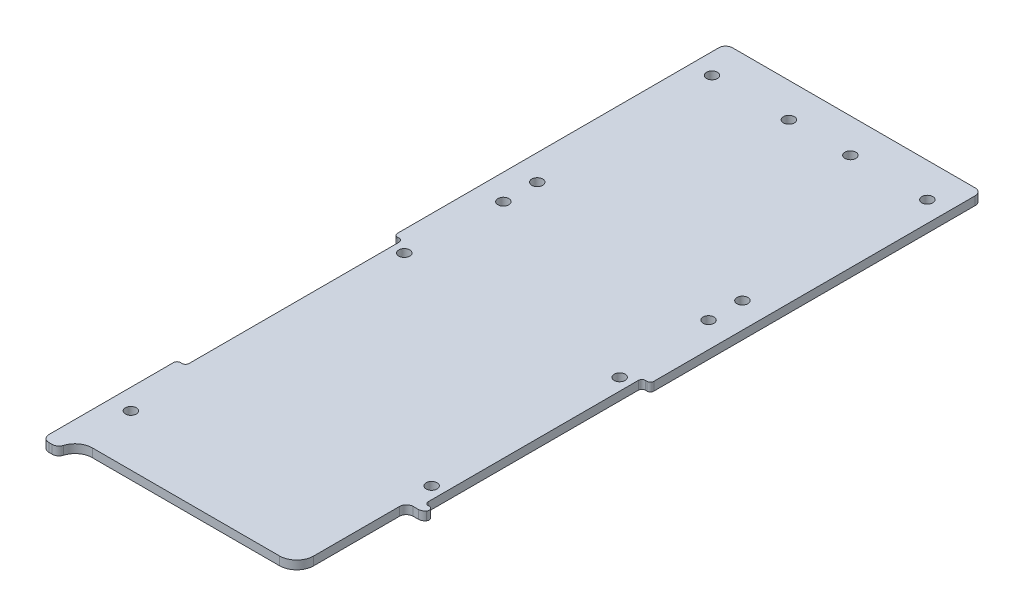
SolidWorks part; units mm, degrees
ref_plane "Front Plane" through (0, 0, 0) normal (0, 0, 1) x (1, 0, 0)
ref_plane "Top Plane" through (0, 0, 0) normal (0, 1, 0) x (1, 0, 0)
ref_plane "Right Plane" through (0, 0, 0) normal (1, 0, 0) x (0, 0, -1)
sketch "Sketch1" plane through (0, 0, 0) normal (0, 1, 0) x (1, 0, 0)
  line L0 (-39.9997, 0) -> (-39.9997, 114.3) construction
  line L1 (-47.625, 127) -> (47.625, 127)
  line L2 (-47.625, 127) -> (-47.625, -127)
  line L3 (-47.625, -127) -> (47.625, -127)
  line L4 (47.625, 127) -> (47.625, -127)
  line L5 (-47.625, 127) -> (47.625, -127) construction
  line L6 (-47.625, -127) -> (47.625, 127) construction
  line L7 (0, 0) -> (0, 127) construction
  line L8 (-39.9997, 0) -> (-39.9997, -101.6) construction
  line L9 (-39.9997, 0) -> (0, 0) construction
  line L10 (-41.275, -127) -> (-41.275, -120.65)
  line L11 (-41.275, -120.65) -> (41.275, -120.65)
  line L12 (41.275, -120.65) -> (41.275, -127)
  line L13 (-39.9997, 114.3) -> (-11.4247, 114.3) construction
  line L14 (39.9997, 114.3) -> (11.4247, 114.3) construction
  circle A0 centre (-39.9997, 114.3) radius 2.032
  circle A1 centre (-39.9997, 0) radius 2.032
  circle A2 centre (-39.9997, -101.6) radius 2.032
  circle A3 centre (39.9997, -101.6) radius 2.032
  circle A4 centre (39.9997, 0) radius 2.032
  circle A5 centre (39.9997, 114.3) radius 2.032
  circle A6 centre (-11.4247, 114.3) radius 2.032
  circle A7 centre (11.4247, 114.3) radius 2.032
  circle A8 centre (-39.9997, -69.85) radius 2.032
  circle A9 centre (39.9997, -69.85) radius 2.032
  point P0 (0, 0)
  dimension "D4" = 4.064
  dimension "D10" = 28.575
  dimension "D1" = 95.25
  dimension "D2" = 254
  dimension "D3" = 7.6253
  dimension "D5" = 12.7
  dimension "D6" = 25.4
  dimension "D7" = 6.35
  dimension "D8" = 6.35
  dimension "D9" = 6.35
  dimension "D11" = 69.85
extrude "Boss-Extrude1" add sketch "Sketch1" along normal blind 3.175 contours L4 L1 L2 L3 A4 A0 A1 A2 A3 A5 | A8 | A3 region at (0, 0, -2.6944) region at (39.9997, 0, 101.6) region at (-39.9997, 0, 69.85)
fillet "Fillet1" radius 2.54 4 edges at (-47.625, 1.5875, -127) (47.625, 1.5875, -127) (47.625, 1.5875, 127) (-47.625, 1.5875, 127)
fillet "Fillet2" radius 2.54 2 edges at (41.275, 1.5875, 127) (-41.275, 1.5875, 127)
fillet "Fillet3" radius 6.35 2 edges at (41.275, 1.5875, 120.65) (-41.275, 1.5875, 120.65)
sketch "Sketch2" plane through (0, 0, 0) normal (0, -1, 0) x (1, 0, 0)
  line L1 (43.815, 127) -> (45.085, 127) construction
  line L2 (40.6451, 123.5787) -> (40.6451, 79.8881)
  line L3 (40.6451, 79.8881) -> (47.625, 79.8881)
  line L11 (47.625, -124.46) -> (47.625, 124.46) construction
  line L12 (43.815, 127) -> (45.085, 127)
  line L13 (47.625, 79.8881) -> (47.625, 124.46)
  arc A0 (35.2956, 120.65) -> (41.3809, 125.1857) centre (35.2956, 127) ccw construction
  arc A1 (43.815, 127) -> (41.3809, 125.1857) centre (43.815, 124.46) ccw construction
  arc A2 (47.625, 124.46) -> (45.085, 127) centre (45.085, 124.46) ccw construction
  arc A3 (40.6451, 123.5787) -> (41.3809, 125.1857) centre (35.2956, 127) ccw
  arc A4 (43.815, 127) -> (41.3809, 125.1857) centre (43.815, 124.46) ccw
  arc A5 (47.625, 124.46) -> (45.085, 127) centre (45.085, 124.46) ccw
  dimension "D2" = 47.1119
  dimension "D1" = 6.9799
extrude "Cut-Extrude1" cut sketch "Sketch2" against normal through all
fillet "Fillet4" radius 6.35 1 edges at (40.6451, 1.5875, 123.5787)
fillet "Fillet5" radius 2.54 2 edges at (47.625, 1.5875, 79.8881) (40.6451, 1.5875, 79.8881)
sketch "Sketch3" plane through (0, 0, 0) normal (0, -1, 0) x (1, 0, 0)
  line L0 (-36.305, -49.7791) -> (-39.9118, -49.7791) construction
  line L1 (-40.4198, -49.276) -> (-40.4198, -45.7043) construction
  line L2 (-35.797, -45.7043) -> (-35.797, -49.276) construction
  line L3 (-39.9118, -45.2013) -> (-36.305, -45.2013) construction
  line L4 (-36.305, -37.2027) -> (-39.9118, -37.2027) construction
  line L5 (-35.797, -33.1279) -> (-35.797, -36.6996) construction
  line L6 (-40.4198, -36.6996) -> (-40.4198, -33.1279) construction
  line L7 (-39.9118, -32.6249) -> (-36.305, -32.6249) construction
  line L8 (36.2882, -32.6249) -> (39.895, -32.6249) construction
  line L9 (40.403, -33.1279) -> (40.403, -36.6996) construction
  line L10 (39.895, -37.2027) -> (36.2882, -37.2027) construction
  line L11 (35.7802, -36.6996) -> (35.7802, -33.1279) construction
  line L12 (36.2882, -45.2013) -> (39.895, -45.2013) construction
  line L13 (35.7802, -49.276) -> (35.7802, -45.7043) construction
  line L14 (40.403, -45.7043) -> (40.403, -49.276) construction
  line L15 (39.895, -49.7791) -> (36.2882, -49.7791) construction
  line L16 (-36.305, -49.7791) -> (-39.9118, -49.7791)
  line L17 (-40.4198, -49.276) -> (-40.4198, -45.7043)
  line L18 (-35.797, -45.7043) -> (-35.797, -49.276)
  line L19 (-39.9118, -45.2013) -> (-36.305, -45.2013)
  line L20 (-36.305, -37.2027) -> (-39.9118, -37.2027)
  line L21 (-35.797, -33.1279) -> (-35.797, -36.6996)
  line L22 (-40.4198, -36.6996) -> (-40.4198, -33.1279)
  line L23 (-39.9118, -32.6249) -> (-36.305, -32.6249)
  line L24 (36.2882, -32.6249) -> (39.895, -32.6249)
  line L25 (40.403, -33.1279) -> (40.403, -36.6996)
  line L26 (39.895, -37.2027) -> (36.2882, -37.2027)
  line L27 (35.7802, -36.6996) -> (35.7802, -33.1279)
  line L28 (36.2882, -45.2013) -> (39.895, -45.2013)
  line L29 (35.7802, -49.276) -> (35.7802, -45.7043)
  line L30 (40.403, -45.7043) -> (40.403, -49.276)
  line L31 (39.895, -49.7791) -> (36.2882, -49.7791)
  line L32 (-47.625, -25.836) -> (47.625, -25.836)
  line L33 (-47.625, -124.46) -> (-47.625, 124.46) construction
  line L34 (47.625, -124.46) -> (47.625, 77.3481) construction
  line L35 (0, -25.836) -> (0, -56.0686) construction
  line L1362 (-40.4198, -34.9138) -> (-35.797, -34.9138)
  line L1857 (-38.1084, -32.6249) -> (-38.1084, -37.2027)
  line L1858 (-38.1084, -45.2013) -> (-38.1084, -49.7791)
  line L1859 (-40.4198, -47.4902) -> (-35.797, -47.4902)
  circle A0 centre (-38.1084, -34.9138) radius 2.032
  circle A1 centre (-38.1084, -47.4902) radius 2.032
  circle A2 centre (38.1084, -47.4902) radius 2.032
  circle A3 centre (38.1084, -34.9138) radius 2.032
  ellipse E0 centre (-39.9118, -45.7043) end of major axis (-39.4038, -45.7043) minor radius 0.5031 (-39.9118, -45.2013) -> (-40.4198, -45.7043) ccw construction
  ellipse E1 centre (-39.9118, -49.276) end of major axis (-39.4038, -49.276) minor radius 0.5031 (-40.4198, -49.276) -> (-39.9118, -49.7791) ccw construction
  ellipse E6 centre (-36.305, -49.276) end of major axis (-35.797, -49.276) minor radius 0.5031 (-36.305, -49.7791) -> (-35.797, -49.276) ccw construction
  ellipse E7 centre (-36.305, -45.7043) end of major axis (-35.797, -45.7043) minor radius 0.5031 (-35.797, -45.7043) -> (-36.305, -45.2013) ccw construction
  ellipse E8 centre (-39.9118, -36.6996) end of major axis (-39.4038, -36.6996) minor radius 0.5031 (-40.4198, -36.6996) -> (-39.9118, -37.2027) ccw construction
  ellipse E9 centre (-36.305, -36.6996) end of major axis (-35.797, -36.6996) minor radius 0.5031 (-36.305, -37.2027) -> (-35.797, -36.6996) ccw construction
  ellipse E10 centre (-36.305, -33.1279) end of major axis (-35.797, -33.1279) minor radius 0.5031 (-35.797, -33.1279) -> (-36.305, -32.6249) ccw construction
  ellipse E11 centre (-39.9118, -33.1279) end of major axis (-39.4038, -33.1279) minor radius 0.5031 (-39.9118, -32.6249) -> (-40.4198, -33.1279) ccw construction
  ellipse E12 centre (39.895, -33.1279) end of major axis (40.403, -33.1279) minor radius 0.5031 (40.403, -33.1279) -> (39.895, -32.6249) ccw construction
  ellipse E13 centre (36.2882, -33.1279) end of major axis (36.7962, -33.1279) minor radius 0.5031 (36.2882, -32.6249) -> (35.7802, -33.1279) ccw construction
  ellipse E14 centre (39.895, -36.6996) end of major axis (40.403, -36.6996) minor radius 0.5031 (39.895, -37.2027) -> (40.403, -36.6996) ccw construction
  ellipse E15 centre (36.2882, -36.6996) end of major axis (36.7962, -36.6996) minor radius 0.5031 (35.7802, -36.6996) -> (36.2882, -37.2027) ccw construction
  ellipse E16 centre (36.2882, -45.7043) end of major axis (36.7962, -45.7043) minor radius 0.5031 (36.2882, -45.2013) -> (35.7802, -45.7043) ccw construction
  ellipse E17 centre (36.2882, -49.276) end of major axis (36.7962, -49.276) minor radius 0.5031 (35.7802, -49.276) -> (36.2882, -49.7791) ccw construction
  ellipse E18 centre (39.895, -45.7043) end of major axis (40.403, -45.7043) minor radius 0.5031 (40.403, -45.7043) -> (39.895, -45.2013) ccw construction
  ellipse E19 centre (39.895, -49.276) end of major axis (40.403, -49.276) minor radius 0.5031 (39.895, -49.7791) -> (40.403, -49.276) ccw construction
  ellipse E20 centre (-39.9118, -45.7043) end of major axis (-39.4038, -45.7043) minor radius 0.5031 (-39.9118, -45.2013) -> (-40.4198, -45.7043) ccw
  ellipse E21 centre (-39.9118, -49.276) end of major axis (-39.4038, -49.276) minor radius 0.5031 (-40.4198, -49.276) -> (-39.9118, -49.7791) ccw
  ellipse E22 centre (-36.305, -49.276) end of major axis (-35.797, -49.276) minor radius 0.5031 (-36.305, -49.7791) -> (-35.797, -49.276) ccw
  ellipse E23 centre (-36.305, -45.7043) end of major axis (-35.797, -45.7043) minor radius 0.5031 (-35.797, -45.7043) -> (-36.305, -45.2013) ccw
  ellipse E24 centre (-39.9118, -36.6996) end of major axis (-39.4038, -36.6996) minor radius 0.5031 (-40.4198, -36.6996) -> (-39.9118, -37.2027) ccw
  ellipse E25 centre (-36.305, -36.6996) end of major axis (-35.797, -36.6996) minor radius 0.5031 (-36.305, -37.2027) -> (-35.797, -36.6996) ccw
  ellipse E26 centre (-36.305, -33.1279) end of major axis (-35.797, -33.1279) minor radius 0.5031 (-35.797, -33.1279) -> (-36.305, -32.6249) ccw
  ellipse E27 centre (-39.9118, -33.1279) end of major axis (-39.4038, -33.1279) minor radius 0.5031 (-39.9118, -32.6249) -> (-40.4198, -33.1279) ccw
  ellipse E28 centre (39.895, -33.1279) end of major axis (40.403, -33.1279) minor radius 0.5031 (40.403, -33.1279) -> (39.895, -32.6249) ccw
  ellipse E29 centre (36.2882, -33.1279) end of major axis (36.7962, -33.1279) minor radius 0.5031 (36.2882, -32.6249) -> (35.7802, -33.1279) ccw
  ellipse E30 centre (39.895, -36.6996) end of major axis (40.403, -36.6996) minor radius 0.5031 (39.895, -37.2027) -> (40.403, -36.6996) ccw
  ellipse E31 centre (36.2882, -36.6996) end of major axis (36.7962, -36.6996) minor radius 0.5031 (35.7802, -36.6996) -> (36.2882, -37.2027) ccw
  ellipse E32 centre (36.2882, -45.7043) end of major axis (36.7962, -45.7043) minor radius 0.5031 (36.2882, -45.2013) -> (35.7802, -45.7043) ccw
  ellipse E33 centre (36.2882, -49.276) end of major axis (36.7962, -49.276) minor radius 0.5031 (35.7802, -49.276) -> (36.2882, -49.7791) ccw
  ellipse E34 centre (39.895, -45.7043) end of major axis (40.403, -45.7043) minor radius 0.5031 (40.403, -45.7043) -> (39.895, -45.2013) ccw
  ellipse E35 centre (39.895, -49.276) end of major axis (40.403, -49.276) minor radius 0.5031 (39.895, -49.7791) -> (40.403, -49.276) ccw
  dimension "D2" = 4.064
extrude "Cut-Extrude2" cut sketch "Sketch3" against normal through all contours A0 | A1 | A2 | A3
sketch "Sketch4" plane through (0, 3.175, 0) normal (0, 1, 0) x (1, 0, 0)
  line L11 (-47.625, 124.46) -> (-47.625, -124.46) construction
  line L12 (-47.625, -76.835) -> (-44.45, -76.835)
  line L13 (-47.625, -76.835) -> (-47.625, 3.81)
  line L15 (-47.625, 3.81) -> (-44.45, 3.81)
  line L16 (-44.45, -76.835) -> (-44.45, 3.81)
  line L17 (47.625, 124.46) -> (47.625, -77.3481) construction
  line L18 (47.625, -76.835) -> (44.45, -76.835)
  line L19 (47.625, -76.835) -> (47.625, 3.81)
  line L20 (47.625, 3.81) -> (44.45, 3.81)
  line L45 (44.45, -76.835) -> (44.45, 3.81)
  line L47 (43.1851, -79.8881) -> (45.085, -79.8881) construction
  dimension "D1" = 3.175
  dimension "D2" = 80.645
  dimension "D3" = 3.0531
extrude "Cut-Extrude3" cut sketch "Sketch4" against normal through all and the other way through all
fillet "Fillet6" radius 1.27 8 edges at (-44.45, 1.5875, -3.81) (-47.625, 1.5875, -3.81) (-47.625, 1.5875, 76.835) (-44.45, 1.5875, 76.835) (44.45, 1.5875, 76.835) (47.625, 1.5875, 76.835) (44.45, 1.5875, -3.81) (47.625, 1.5875, -3.81)
